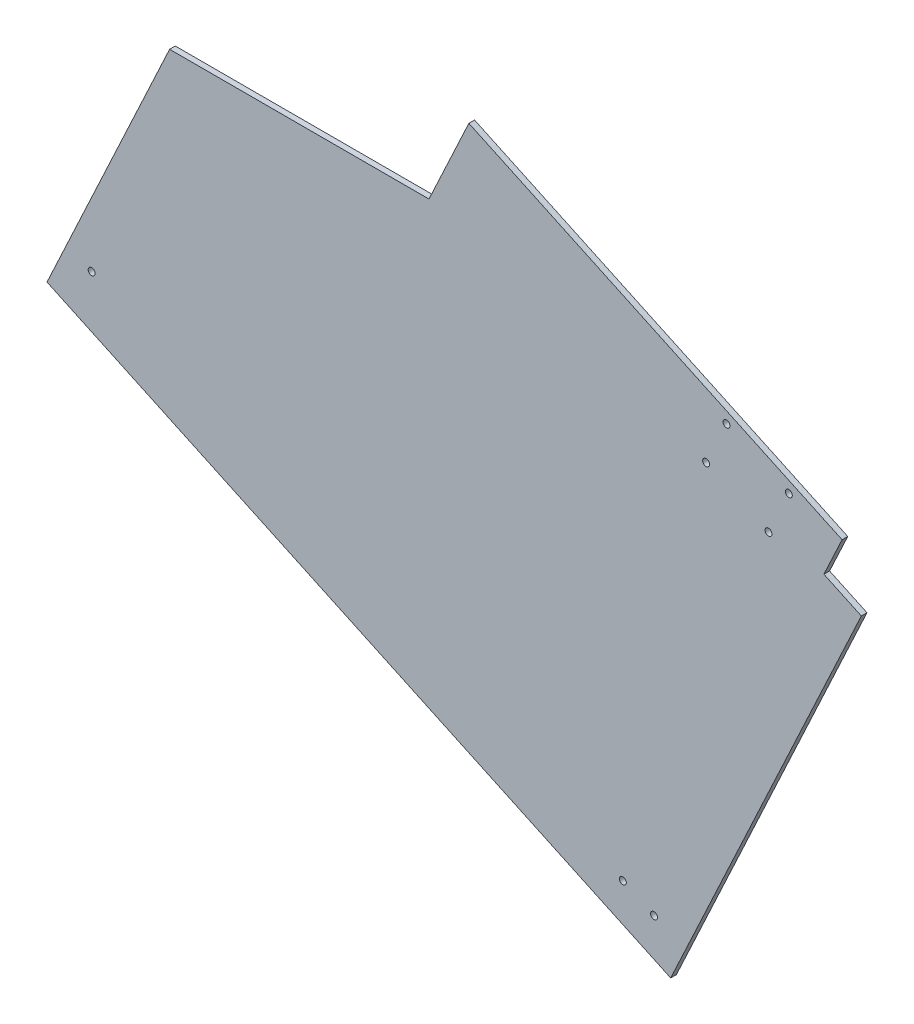
SolidWorks part; units mm, degrees
ref_plane "Front Plane" through (0, 0, 0) normal (0, 0, 1) x (1, 0, 0)
ref_plane "Top Plane" through (0, 0, 0) normal (0, 1, 0) x (1, 0, 0)
ref_plane "Right Plane" through (0, 0, 0) normal (1, 0, 0) x (0, 0, -1)
sketch "Sketch1" plane through (0, 0, 0) normal (0, 0, 1) x (1, 0, 0)
  line L0 (-261.1014, 0.0035) -> (-110.3324, 0.0035)
  line L1 (-110.3324, 0.0035) -> (-87.1479, 49.7228)
  line L2 (-87.1479, 49.7228) -> (129.7831, -51.4338)
  line L3 (129.7831, -51.4338) -> (119.2177, -74.0915)
  line L4 (119.2177, -74.0915) -> (140.969, -84.2344)
  line L5 (140.969, -84.2344) -> (30.1585, -321.8683)
  line L6 (30.1585, -321.8683) -> (-332.3646, -152.8209)
  line L7 (-332.3646, -152.8209) -> (-261.1014, 0.0035)
  line L8 (-257.4117, 0.0035) -> (-57.4117, 0.0035) construction
  line L9 (-332.3646, -152.8209) -> (-261.0998, 0.0069) construction
  line L10 (30.1585, -321.8683) -> (-332.3646, -152.8209) construction
  line L11 (140.969, -84.2344) -> (30.1585, -321.8683) construction
  line L12 (-189.2372, 97.3278) -> (129.7831, -51.4338) construction
  line L13 (119.2177, -74.0915) -> (140.969, -84.2344) construction
  line L14 (129.7831, -51.4338) -> (119.2177, -74.0915) construction
  line L15 (-110.3324, 0.0035) -> (-87.1479, 49.7228) construction
  circle A0 centre (87.0035, -69.0002) radius 2
  circle A1 centre (98.8369, -43.6236) radius 2
  circle A2 centre (62.5845, -26.7189) radius 2
  circle A3 centre (50.7512, -52.0955) radius 2
  circle A4 centre (2.3586, -286.8374) radius 2
  circle A5 centre (-306.4229, -134.5749) radius 2
  circle A6 centre (20.4847, -295.2897) radius 2
  circle A7 centre (2.3586, -286.8374) radius 2 construction
  circle A8 centre (20.4847, -295.2897) radius 2 construction
  dimension "D1" = 4
  dimension "D2" = 4
  dimension "D3" = 4
  dimension "D4" = 4
  dimension "D7" = 4
  dimension "D5" = 27.5
  dimension "D6" = 15.8
extrude "Boss-Extrude1" add sketch "Sketch1" along normal up to surface (3.3 mm away)
